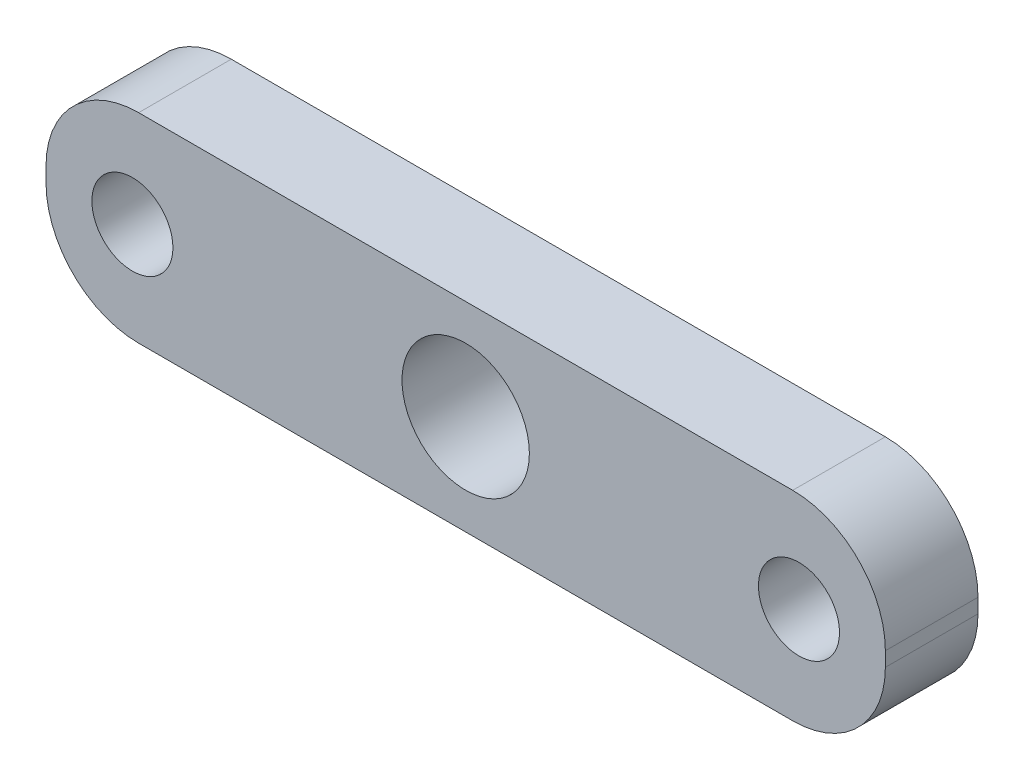
SolidWorks part; units mm, degrees
ref_plane "Front Plane" through (0, 0, 0) normal (0, 0, 1) x (1, 0, 0)
ref_plane "Top Plane" through (0, 0, 0) normal (0, 1, 0) x (1, 0, 0)
ref_plane "Right Plane" through (0, 0, 0) normal (1, 0, 0) x (0, 0, -1)
sketch "Sketch1" plane through (0, 0, 0) normal (0, 0, 1) x (1, 0, 0)
  line L0 (19.932, 0) -> (-19.932, 0) construction
  line L1 (18.12, -4.31) -> (-18.12, -4.31)
  line L2 (18.12, -4.31) -> (18.12, 4.31)
  line L3 (18.12, 4.31) -> (-18.12, 4.31)
  line L4 (-18.12, -4.31) -> (-18.12, 4.31)
  circle A0 centre (-14.39, 0) radius 1.75
  circle A1 centre (14.39, 0) radius 1.75
  circle A2 centre (0, 0) radius 2.75
  point P4 (18.12, 0)
  point P6 (0, 4.31)
  dimension "D1" = 3.73
  dimension "D3" = 28.78
  dimension "D2" = 3.73
extrude "Boss-Extrude1" add sketch "Sketch1" along normal blind 4
fillet "Fillet1" radius 4 4 edges at (18.12, -4.31, 2) (18.12, 4.31, 2) (-18.12, 4.31, 2) (-18.12, -4.31, 2)
